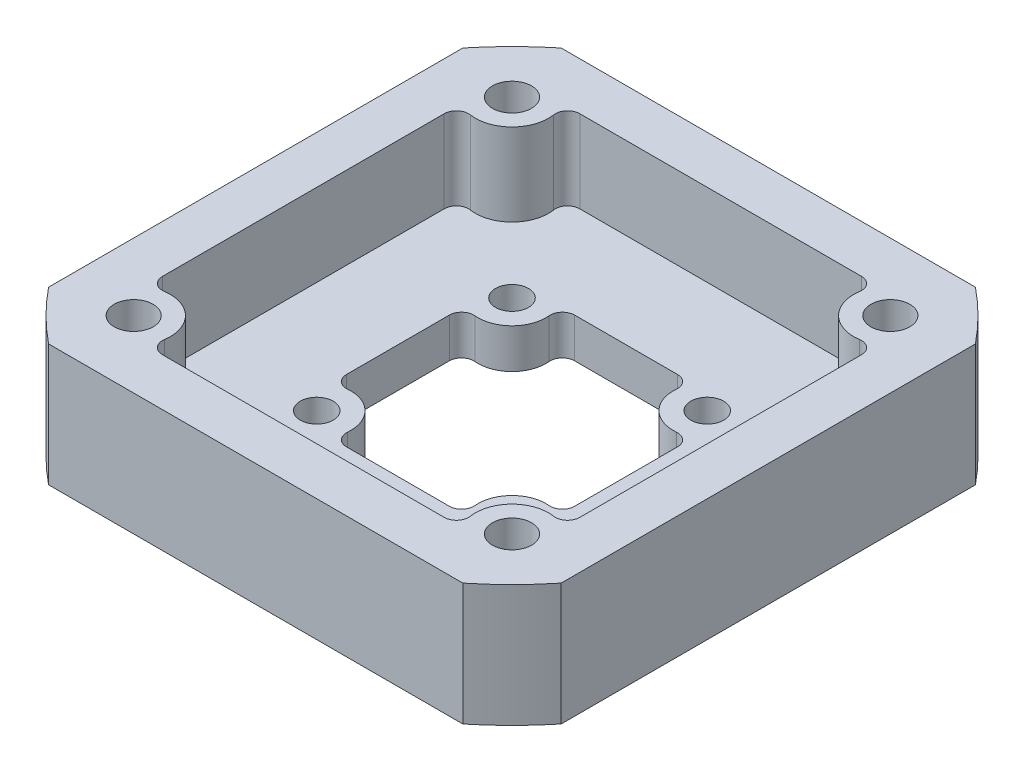
SolidWorks part; units mm, degrees
ref_plane "Front Plane" through (0, 0, 0) normal (0, 0, 1) x (1, 0, 0)
ref_plane "Top Plane" through (0, 0, 0) normal (0, 1, 0) x (1, 0, 0)
ref_plane "Right Plane" through (0, 0, 0) normal (1, 0, 0) x (0, 0, -1)
sketch "Sketch1" plane through (0, 0, 0) normal (0, 1, 0) x (1, 0, 0)
  line L0 (-16.971, 21) -> (16.971, 21)
  line L1 (21, 16.971) -> (21, -16.971)
  line L2 (16.971, -21) -> (-16.971, -21)
  line L3 (-21, 16.971) -> (-21, -16.971)
  line L4 (-0.0002, 0.0002) -> (0, 0) construction
  line L5 (0, 0) -> (0.0002, -0.0002) construction
  line L6 (0.0002, 0.0002) -> (0, 0) construction
  line L7 (0, 0) -> (-0.0002, -0.0002) construction
  line L8 (-17.1, 12.9623) -> (-17.1, -12.9623)
  line L9 (-12.9623, -17.1) -> (12.9623, -17.1)
  line L11 (-12.9623, 17.1) -> (12.9623, 17.1)
  line L12 (-5.5471, 9.3498) -> (5.5467, 9.3498)
  line L13 (9.3498, 5.5467) -> (9.3498, -5.5471)
  line L14 (-9.3502, 5.5467) -> (-9.3502, -5.5471)
  line L15 (-5.5471, -9.3502) -> (5.5467, -9.3502)
  line L16 (-8.0002, 7.9998) -> (-0.0002, -0.0002) construction
  line L17 (-0.0002, -0.0002) -> (7.9998, -8.0002) construction
  line L18 (7.9998, 7.9998) -> (-0.0002, -0.0002) construction
  line L19 (-0.0002, -0.0002) -> (-8.0002, -8.0002) construction
  line L20 (17.1, 12.9623) -> (17.1, -12.9623)
  arc A4 (16.971, 21) -> (21, 16.971) centre (0.0002, 0.0002) cw
  arc A5 (-16.971, 21) -> (-21, 16.971) centre (-0.0002, 0.0002) ccw
  arc A6 (21, -16.971) -> (16.971, -21) centre (0.0002, -0.0002) cw
  arc A7 (-21, -16.971) -> (-16.971, -21) centre (-0.0002, -0.0002) ccw
  circle A8 centre (-15.5, 15.5) radius 1.6
  circle A9 centre (15.5, 15.5) radius 1.6
  circle A10 centre (15.5, -15.5) radius 1.6
  circle A11 centre (-15.5, -15.5) radius 1.6
  arc A12 (-17.1, 12.9623) -> (-12.9623, 17.1) centre (-15.5, 15.5) ccw
  arc A13 (12.9623, 17.1) -> (17.1, 12.9623) centre (15.5, 15.5) ccw
  arc A14 (12.9623, -17.1) -> (17.1, -12.9623) centre (15.5, -15.5) cw
  arc A15 (-12.9623, -17.1) -> (-17.1, -12.9623) centre (-15.5, -15.5) ccw
  circle A16 centre (-8.0002, 7.9998) radius 1.35
  circle A17 centre (7.9998, 7.9998) radius 1.35
  circle A18 centre (7.9998, -8.0002) radius 1.35
  circle A19 centre (-8.0002, -8.0002) radius 1.35
  arc A20 (-9.3502, 5.5467) -> (-5.5471, 9.3498) centre (-8.0002, 7.9998) ccw
  arc A21 (-9.3502, -5.5471) -> (-5.5471, -9.3502) centre (-8.0002, -8.0002) cw
  arc A22 (5.5467, -9.3502) -> (9.3498, -5.5471) centre (7.9998, -8.0002) cw
  arc A23 (9.3498, 5.5467) -> (5.5467, 9.3498) centre (7.9998, 7.9998) cw
  dimension "D1" = 42
  dimension "D4" = 27
  dimension "D7" = 3.2
  dimension "D8" = 2.7
  dimension "D11" = 2.8
  dimension "D12" = 3
  dimension "D2" = 42
  dimension "D3" = 33.942
  dimension "D5" = 31
  dimension "D6" = 31
  dimension "D9" = 16
  dimension "D10" = 16
extrude "Boss-Extrude1" add sketch "Sketch1" along normal blind 10 contours L9 A15 L8 A12 L11 A13 L20 L1 A4 L0 A5 L3 A7 L2 A6 A14 A8 A9 A10 A11 region at (0, 0, -20.406)
extrude "Boss-Extrude2" add sketch "Sketch1<3>" along normal blind 3.25 contours A15 L9 A14 L1 L20 A13 L11 A12 L8 A23 L13 A22 L15 A21 L14 A20 L12 A19 A18 A17 A16 region at (-13.0367, 0, -13.0367)
sketch "Sketch1<3>" plane through (0, 0, 0) normal (0, 1, 0) x (1, 0, 0) same geometry as "Sketch1"
fillet "Fillet1" radius 1 16 edges at (12.9623, 6.625, 17.1) (17.1, 6.625, -12.9623) (12.9623, 6.625, -17.1) (-12.9623, 6.625, -17.1) (-17.1, 6.625, -12.9623) (-17.1, 6.625, 12.9623) (-12.9623, 6.625, 17.1) (-5.5471, 1.625, 9.3502) (-9.3502, 1.625, 5.5471) (5.5467, 1.625, 9.3502) (9.3498, 1.625, 5.5471) (9.3498, 1.625, -5.5467) (5.5467, 1.625, -9.3498) (-5.5471, 1.625, -9.3498) (-9.3502, 1.625, -5.5467) (17.1, 6.625, 12.9623)
